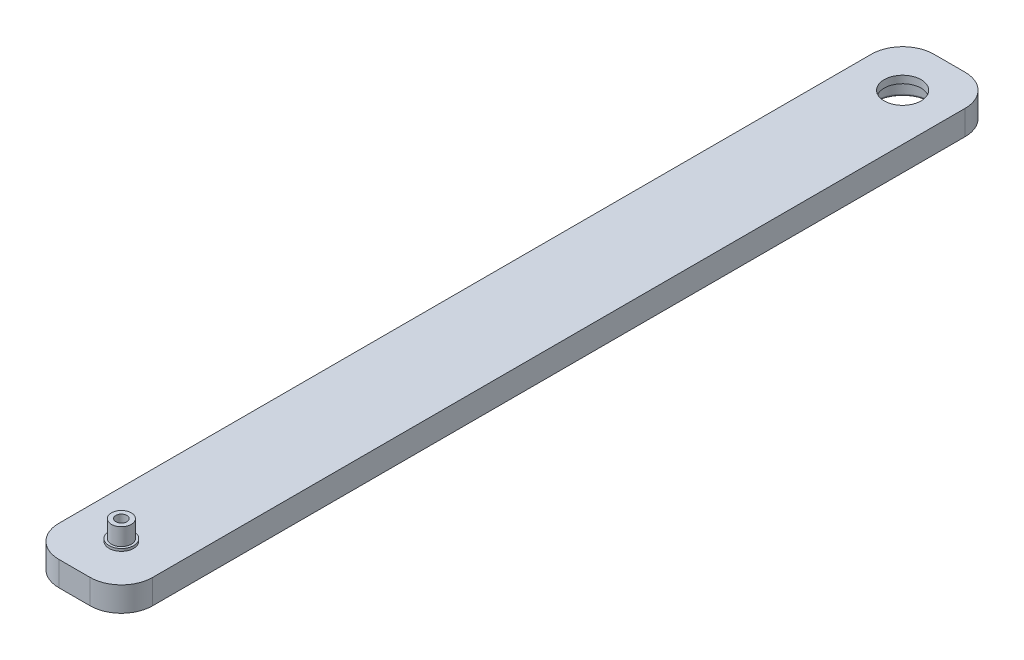
SolidWorks part; units mm, degrees
ref_plane "Front Plane" through (0, 0, 0) normal (0, 0, 1) x (1, 0, 0)
ref_plane "Top Plane" through (0, 0, 0) normal (0, 1, 0) x (1, 0, 0)
ref_plane "Right Plane" through (0, 0, 0) normal (1, 0, 0) x (0, 0, -1)
sketch "Sketch1" plane through (0, 0, 0) normal (0, 1, 0) x (1, 0, 0)
  line L1 (-19.05, -177.8) -> (19.05, -177.8)
  line L2 (-19.05, -177.8) -> (-19.05, 177.8)
  line L3 (-19.05, 177.8) -> (19.05, 177.8)
  line L4 (19.05, -177.8) -> (19.05, 177.8)
  line L5 (-19.05, -177.8) -> (19.05, 177.8) construction
  line L6 (-19.05, 177.8) -> (19.05, -177.8) construction
  point P0 (0, 0)
  dimension "D1" = 38.1
  dimension "D2" = 355.6
extrude "Boss-Extrude1" add sketch "Sketch1" along normal mid plane 10
fillet "Fillet1" radius 12.7 4 edges at (19.05, 0, -177.8) (-19.05, 0, -177.8) (19.05, 0, 177.8) (-19.05, 0, 177.8)
sketch "Sketch2" plane through (0, 5, 0) normal (0, 1, 0) x (1, 0, 0)
  line L0 (0, 158.75) -> (0, 177.8) construction
  line L1 (6.35, 177.8) -> (-6.35, 177.8) construction
  circle A0 centre (0, 158.75) radius 11.05
  dimension "D2" = 22.1
  dimension "D1" = 19.05
extrude "Cut-Extrude1" cut sketch "Sketch2" against normal through all
fillet "Fillet2" radius 0.7937 1 edges at (0, -5, -147.7)
sketch "Sketch3" plane through (0, 5, 0) normal (0, 1, 0) x (1, 0, 0)
  line L0 (0, 0) -> (50000, 0) construction
  circle A0 centre (0, -158.75) radius 2.25
  circle A3 centre (0, 158.75) radius 11.05 construction
  point P8 (0, 158.75)
  dimension "D1" = 4.5
extrude "Cut-Extrude2" cut sketch "Sketch3" against normal through all
sketch "Sketch4" plane through (0, 5, 0) normal (0, 1, 0) x (1, 0, 0)
  circle A0 centre (0, -158.75) radius 5
  circle M2 centre (0, -158.75) radius 2.25
  dimension "D1" = 10
extrude "Boss-Extrude2" add sketch "Sketch4" along normal blind 1 contours A0 M2 region at (-4.8586, 5, 158.75)
sketch "Sketch6" plane through (0, 5, 0) normal (0, 1, 0) x (1, 0, 0)
  circle A0 centre (0, 158.75) radius 11.05 construction
  circle A1 centre (0, 158.75) radius 11.05
extrude "Boss-Extrude3" add sketch "Sketch6" against normal offset from surface (3 mm away) 7 up to face at (0, -5, 161)
sketch "Sketch7" plane through (0, 2, 0) normal (0, -1, 0) x (1, 0, 0)
  circle A0 centre (0, -158.75) radius 7.5
  circle A1 centre (0, -158.75) radius 11.05 construction
  dimension "D1" = 15
extrude "Cut-Extrude3" cut sketch "Sketch7" against normal through all
sketch "Sketch8" plane through (0, 6, 0) normal (0, 1, 0) x (1, 0, 0)
  circle A0 centre (0, -158.75) radius 4.05
  circle M1 centre (0, -158.75) radius 2.25
  dimension "D1" = 8.1
extrude "Boss-Extrude4" add sketch "Sketch8" along normal blind 7 contours A0 M1 region at (-3.9354, 6, 158.75)
